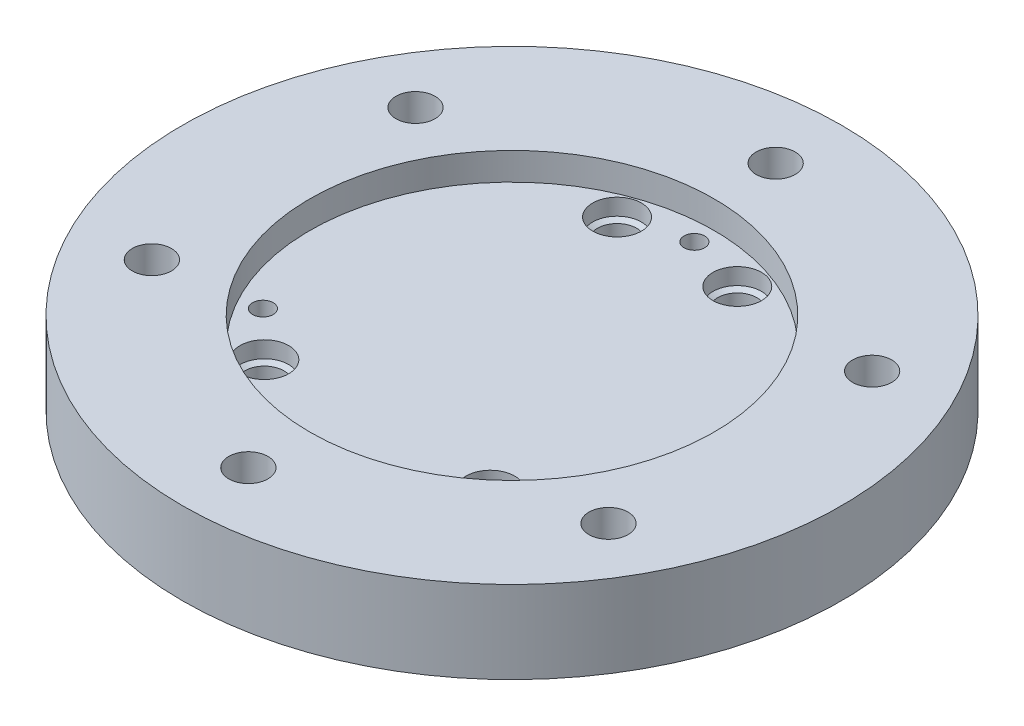
SolidWorks part; units mm, degrees
material "Copper"
ref_plane "Front Plane" through (0, 0, 0) normal (0, 0, 1) x (1, 0, 0)
ref_plane "Top Plane" through (0, 0, 0) normal (0, 1, 0) x (1, 0, 0)
ref_plane "Right Plane" through (0, 0, 0) normal (1, 0, 0) x (0, 0, -1)
ref_axis "Y Axis" through (0, 0.1588, 0) along (0, -1, 0)
sketch "outer" plane through (0, 0, 0) normal (0, 1, 0) x (1, 0, 0)
  circle A0 centre (0, 0) radius 19.05
  dimension "D1" = 38.1
extrude "Body" add sketch "outer" against normal blind 4.7625
sketch "inner" plane through (0, 0, 0) normal (0, 1, 0) x (1, 0, 0)
  circle A0 centre (0, 0) radius 11.684
  dimension "D1" = 23.368
extrude "Pocket" cut sketch "inner" against normal blind 1.5875
sketch "Screw Position" plane through (0, 0, 0) normal (0, 1, 0) x (1, 0, 0)
  point P0 (0, -15.24)
  dimension "D1" = 15.24
hole_wizard "#4-40 Tapped Hole3" positions "Sketch12" profile "Sketch13" tap size "#4-40" standard "ANSI Inch" end condition through all
sketch "Sketch12" plane through (0, 0, 0) normal (0, 1, 0) x (1, 0, 0)
  point P0 (0, -15.24)
sketch "Sketch13" plane through (0, 0, 15.24) normal (1, 0, 0) x (0, 0, 1)
  line L0 (0, 0) -> (0, 4.7625)
  line L1 (0, 4.7625) -> (1.1303, 4.7625)
  line L2 (1.1303, 4.7625) -> (1.1303, 0)
  line L5 (1.1303, 0) -> (0, 0)
  line L11 (0, -6.35) -> (0, 107.95) construction
  dimension "Thru Tap Drill Dia." = 2.2606
  dimension "Thru Tap Drill Depth" = 4.7625
cosmetic thread "Hole Thread3" parameters "D2"=2.8448
pattern_circular "Screw Holes" count 6 over 360 about axis through (0, 0.1588, 0) along (0, -1, 0) of "#4-40 Tapped Hole3"
sketch "Inner Screw Position" plane through (0, 0, 0) normal (0, 1, 0) x (1, 0, 0)
  point P0 (0, 10.541)
  dimension "D1" = 10.541
hole_wizard "#0-80 Tapped Hole1" positions "Sketch16" profile "Sketch17" tap size "#0-80" standard "ANSI Inch" end condition through all
sketch "Sketch16" plane through (0, -1.5875, 0) normal (0, 1, 0) x (1, 0, 0)
  point P0 (0, 10.541)
sketch "Sketch17" plane through (0, -1.5875, -10.541) normal (1, 0, 0) x (0, 0, 1)
  line L0 (0, 0) -> (0, 3.175)
  line L1 (0, 3.175) -> (0.5956, 3.175)
  line L2 (0.5956, 3.175) -> (0.5956, 0)
  line L5 (0.5956, 0) -> (0, 0)
  line L11 (0, -6.35) -> (0, 107.95) construction
  dimension "Thru Tap Drill Dia." = 1.1913
  dimension "Thru Tap Drill Depth" = 3.175
cosmetic thread "Hole Thread4" parameters "D2"=1.524
pattern_circular "Inner Screw Holes" count 3 over 360 about axis through (0, 0.1588, 0) along (0, -1, 0) of "#0-80 Tapped Hole1"
sketch "IO Postion" plane through (0, 0, 0) normal (0, 1, 0) x (1, 0, 0)
  line L0 (0, 0) -> (-3.4749, 9.5473) construction
  line L1 (0, 0) -> (-5.9719, 8.2196) construction
  point P0 (-3.4749, 9.5473)
  point P5 (-5.9719, 8.2196)
  point P6 (-8.0062, 6.2551)
  point P7 (-9.4202, 3.806)
  point P8 (-10.1043, 1.062)
  point P9 (-10.0056, -1.7643)
  point P13 (10.0056, -1.7643)
  point P14 (10.1043, 1.062)
  point P15 (9.4202, 3.806)
  point P16 (8.0062, 6.2551)
  point P17 (5.9719, 8.2196)
  point P18 (3.4749, 9.5473)
  point P19 (-6.5307, -7.783)
  point P20 (-4.1324, -9.2816)
  point P21 (-1.414, -10.0611)
  point P22 (1.414, -10.0611)
  point P23 (4.1324, -9.2816)
  point P24 (6.5307, -7.783)
  point P25 (0, 0)
  dimension "D3" = 16
  dimension "D2" = 6
  dimension "D4" = 3
hole_wizard "#43 (0.089) Diameter Hole1" positions "Sketch20" profile "Sketch21" hole size "#43" standard "ANSI Inch" end condition through all
sketch "Sketch20" plane through (0, -1.5875, 0) normal (0, 1, 0) x (1, 0, 0)
  point P0 (-3.4749, 9.5473)
sketch "Sketch21" plane through (-3.4749, -1.5875, -9.5473) normal (1, 0, 0) x (0, 0, 1)
  line L0 (0, 0) -> (0, 3.175)
  line L1 (0, 3.175) -> (1.1303, 3.175)
  line L2 (1.1303, 3.175) -> (1.1303, 0)
  line L5 (1.1303, 0) -> (0, 0)
  line L11 (0, -6.35) -> (0, 107.95) construction
  dimension "Thru Hole Dia." = 2.2606
  dimension "Thru Hole Depth" = 3.175
hole_wizard "#34 (0.111) Diameter Hole1" positions "Sketch22" profile "Sketch23" hole size "#34" standard "ANSI Inch"
sketch "Sketch22" plane through (0, -1.5875, 0) normal (0, 1, 0) x (1, 0, 0)
  point P0 (-3.4749, 9.5473)
sketch "Sketch23" plane through (-3.4749, -1.5875, -9.5473) normal (1, 0, 0) x (0, 0, 1)
  line L0 (0, 0) -> (0, 1.7995)
  line L1 (0, 1.7995) -> (1.4097, 0.9525)
  line L2 (1.4097, 0.9525) -> (1.4097, 0)
  line L5 (1.4097, 0) -> (0, 0)
  line L10 (0, 1.7995) -> (-1.4097, 0.9525) construction
  line L11 (0, -6.35) -> (0, 107.95) construction
  dimension "Hole Dia." = 2.8194
  dimension "Hole Depth" = 0.9525
  dimension "Drill Angle" = 118
hole_wizard "#34 (0.111) Diameter Hole2" positions "Sketch28" profile "Sketch27" hole size "#34" standard "ANSI Inch"
sketch "Sketch28" plane through (0, -4.7625, 0) normal (0, -1, 0) x (-1, 0, 0)
  point P0 (3.4749, 9.5473)
sketch "Sketch27" plane through (-3.4749, -4.7625, -9.5473) normal (1, 0, 0) x (0, 0, -1)
  line L0 (0, 0) -> (0, 1.7995)
  line L1 (0, 1.7995) -> (1.4097, 0.9525)
  line L2 (1.4097, 0.9525) -> (1.4097, 0)
  line L5 (1.4097, 0) -> (0, 0)
  line L10 (0, 1.7995) -> (-1.4097, 0.9525) construction
  line L11 (0, -6.35) -> (0, 107.95) construction
  dimension "Hole Dia." = 2.8194
  dimension "Hole Depth" = 0.9525
  dimension "Drill Angle" = 118
sketch "IO Hole Position" plane through (0, 0, 0) normal (0, 1, 0) x (1, 0, 0)
  point P0 (3.4749, 9.5473)
  point P1 (-6.5307, -7.783)
  point P3 (6.5307, -7.783)
pattern_sketch "IO Holes Pattern" of "#43 (0.089) Diameter Hole1", "#34 (0.111) Diameter Hole1", "#34 (0.111) Diameter Hole2" driven by "IO Hole Position"
equation "\"outer_d\"= 3 / 2in"
equation "\"screw_r\"= 0.6in"
equation "\"inner_d\"= 0.920in"
equation "\"bottom_h\"= 3 / 16in"
equation "\"pocket_h\"= 1 / 16in"
equation "\"screw_inner_r\"= 0.415in"
equation "\"io_r\"= 0.4in"
equation "\"D1@outer\" = \"outer_d\""
equation "\"D1@Body\" = \"bottom_h\""
equation "\"D1@inner\" = \"inner_d\""
equation "\"D1@Pocket\"=\"pocket_h\""
equation "\"D1@Screw Position\" = \"screw_r\""
equation "\"D1@Inner Screw Position\" = \"screw_inner_r\""
equation "\"D1@IO Postion\" = \"io_r\""
